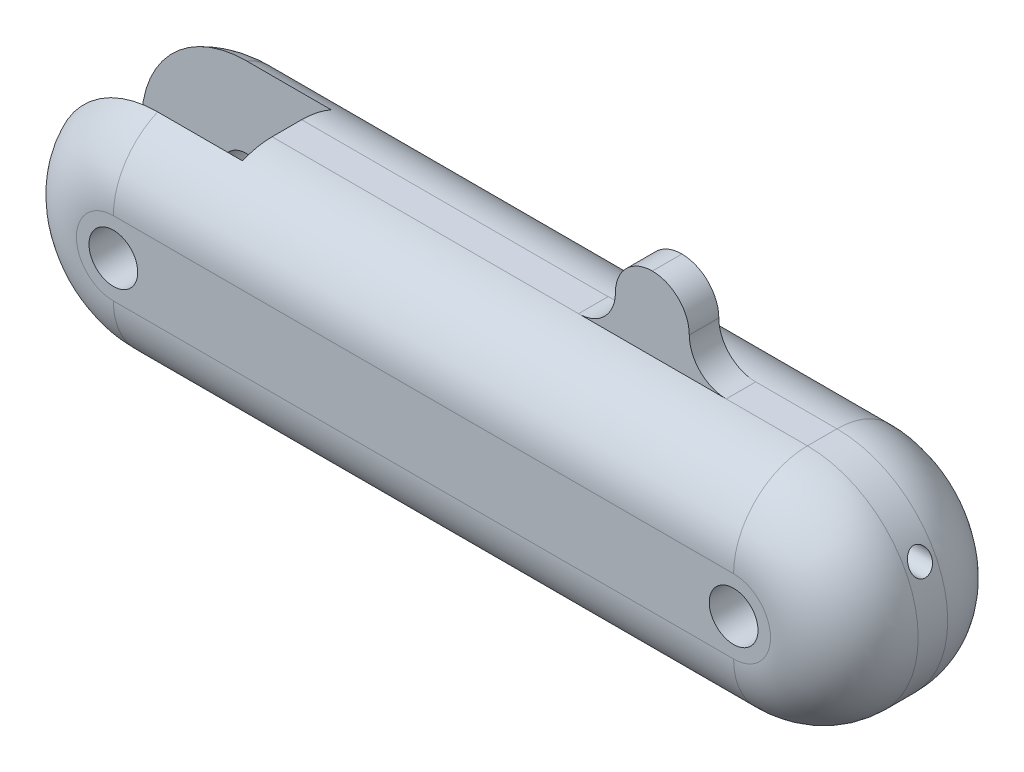
SolidWorks part; units mm, degrees
ref_plane "Front Plane" through (0, 0, 0) normal (0, 0, 1) x (1, 0, 0)
ref_plane "Top Plane" through (0, 0, 0) normal (0, 1, 0) x (1, 0, 0)
ref_plane "Right Plane" through (0, 0, 0) normal (1, 0, 0) x (0, 0, -1)
sketch "Sketch2" plane through (0, 0, 0) normal (0, 0, 1) x (1, 0, 0)
  line L0 (-21, 0) -> (21, 0)
  line L1 (-21, -15) -> (21, -15)
  arc A0 (-21, 0) -> (-21, -15) centre (-21, -7.5) ccw
  arc A1 (21, 0) -> (21, -15) centre (21, -7.5) cw
  point P4 (0, 0)
  dimension "D5" = 7.5
  dimension "D1" = 42
  dimension "D6" = 42
extrude "Boss-Extrude1" add sketch "Sketch2" along normal blind 12
fillet "Fillet1" radius 5 8 edges at (28.5, -7.5, 0) (0, -15, 0) (-28.5, -7.5, 0) (28.5, -7.5, 12) (0, -15, 12) (-28.5, -7.5, 12) (0, 0, 0) (0, 0, 12)
sketch "Sketch3" plane through (0, 0, 12) normal (0, 0, 1) x (1, 0, 0)
  circle A0 centre (-21, -7.5) radius 1.65
  circle A1 centre (21, -7.5) radius 1.65
  arc A2 (-21, 0) -> (-21, -15) centre (-21, -7.5) ccw construction
  point P14 (-28.5, -7.5)
  dimension "D1" = 3.3
ref_plane "Plane1" through (13.5, 0, 0) normal (-1, 0, 0) x (0, 0, 1)
ref_plane "Plane3" through (0, -25, 0) normal (0, -1, 0) x (-1, 0, 0)
sketch "Sketch5" plane through (0, -25, 0) normal (0, -1, 0) x (-1, 0, 0)
  line L0 (-21, 0) -> (21, 0) construction
  line L1 (15.25, -3) -> (28.5, -3)
  line L2 (15.25, -3) -> (15.25, -9)
  line L3 (15.25, -9) -> (28.5, -9)
  line L4 (28.5, -3) -> (28.5, -9)
  line L5 (21, -12) -> (-21, -12) construction
  line L7 (28.5, -7) -> (28.5, -5) construction
  dimension "D1" = 3
  dimension "D2" = 3
  dimension "D3" = 13.25
extrude "Cut-Extrude3" cut sketch "Sketch5" against normal through all
sketch "Sketch6" plane through (0, 0, 0) normal (0, 1, 0) x (1, 0, 0)
  line L0 (13.75, -12) -> (13.75, 0) construction
  line L1 (8, -5) -> (13, -5)
  line L2 (8, -5) -> (8, -7)
  line L3 (8, -7) -> (13, -7)
  line L4 (13, -5) -> (13, -7)
  line L5 (21, -7) -> (21, -12) construction
  line L6 (21, -5) -> (-15.25, -5) construction
  point P4 (13, -6)
  point P7 (13.75, -6)
  dimension "D1" = 5
  dimension "D3" = 8
extrude "Boss-Extrude2" add sketch "Sketch6" along normal blind 5
fillet "Fillet2" radius 2.5 2 edges at (13, 5, 6) (8, 5, 6)
fillet "Fillet3" radius 2.5 2 edges at (8, 0, 6) (13, 0, 6)
extrude "Cut-Extrude4" cut sketch "Sketch3" against normal through all
ref_plane "Plane4" through (28.5, 0, 0) normal (1, 0, 0) x (0, 0, -1)
sketch "Sketch8" plane through (28.5, 0, 0) normal (1, 0, 0) x (0, 0, -1)
  line L0 (-7, -15) -> (-5, -15) construction
  circle A0 centre (-6, -4) radius 0.75
  point P6 (-6, -15)
  dimension "D1" = 1.5
  dimension "D2" = 4
extrude "Cut-Extrude7" cut sketch "Sketch8" against normal through all
sketch "Sketch9" plane through (-15.25, 0, 0) normal (-1, 0, 0) x (0, 0, 1)
  line L1 (7, -15) -> (5, -15) construction
  circle A0 centre (6, -11) radius 0.75
  dimension "D1" = 1.5
  dimension "D2" = 4
sketch "Sketch10" plane through (0, -15, 0) normal (0, -1, 0) x (1, 0, 0)
  line L0 (21, 7) -> (21, 5) construction
  line L2 (21, 12) -> (21, 7) construction
  circle A0 centre (15, 6) radius 0.75
  point P5 (21, 6)
  point P10 (21, 9.5)
  dimension "D1" = 1.5
  dimension "D2" = 6
sketch "Sketch11" plane through (0, 0, 12) normal (0, 0, 1) x (1, 0, 0)
  line L0 (-15.25, -11) -> (15, -15) construction
  line L1 (-15.25, -10.25) -> (-15.25, -11.75) construction
  line L2 (14.25, -15) -> (15.75, -15) construction
extrude "Cut-Extrude9" cut sketch "Sketch9" along direction (0.9914, -0.1311, 0) on the side against the normal up to vertex (30.25 mm away) contours A0 up to point (15, -15, 6)
